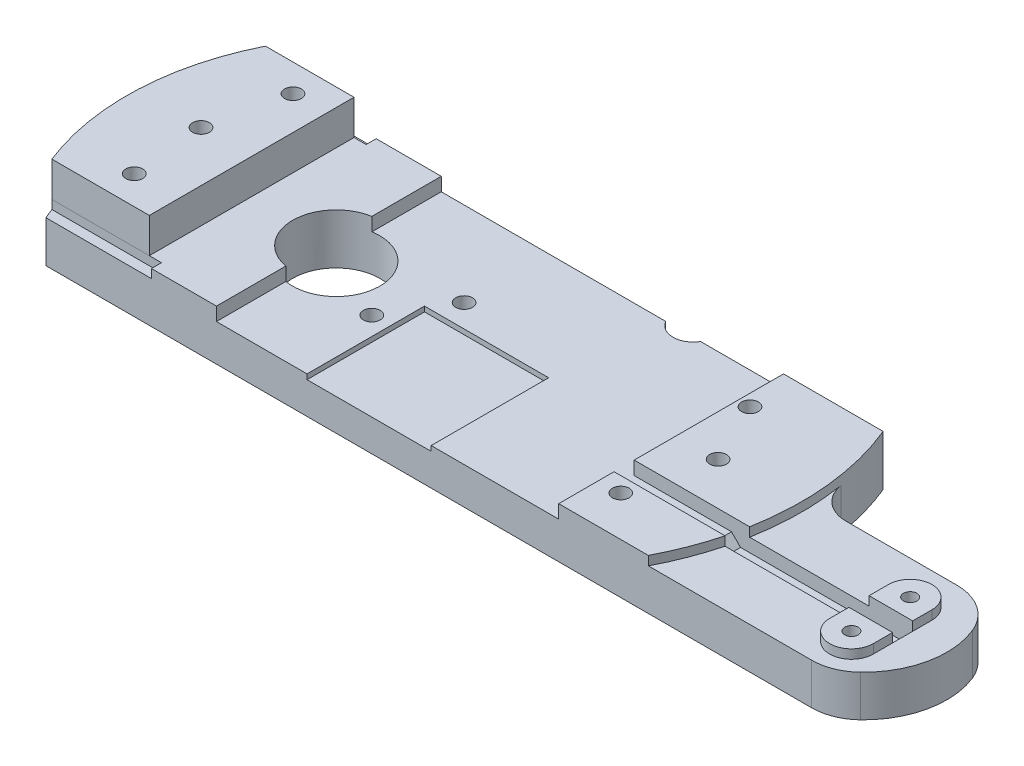
SolidWorks part; units mm, degrees
ref_plane "Front Plane" through (0, 0, 0) normal (0, 0, 1) x (1, 0, 0)
ref_plane "Top Plane" through (0, 0, 0) normal (0, 1, 0) x (1, 0, 0)
ref_plane "Right Plane" through (0, 0, 0) normal (1, 0, 0) x (0, 0, -1)
sketch "Sketch1" plane through (0, 0, 0) normal (0, 1, 0) x (1, 0, 0)
  line L1 (-97.5, -33.5) -> (97.5, -33.5)
  line L2 (-97.5, -33.5) -> (-97.5, 33.5)
  line L3 (-97.5, 33.5) -> (97.5, 33.5)
  line L4 (97.5, -33.5) -> (97.5, 33.5)
  line L5 (-97.5, -33.5) -> (97.5, 33.5) construction
  line L6 (-97.5, 33.5) -> (97.5, -33.5) construction
  point P0 (0, 0)
  dimension "D1" = 67
  dimension "D2" = 195
extrude "Boss-Extrude1" add sketch "Sketch1" along normal blind 25.4
sketch "Sketch2" plane through (0, 0, 0) normal (0, -1, 0) x (1, 0, 0)
  line L0 (-97.5, -33.5) -> (-97.5, 33.5) construction
  line L1 (97.5, 33.5) -> (97.5, -33.5) construction
  line L2 (97.5, 33.5) -> (88.5, 33.5)
  line L3 (-97.5, 33.5) -> (97.5, 33.5) construction
  line L4 (97.5, -33.5) -> (91.5, -33.5)
  line L5 (97.5, -33.5) -> (-97.5, -33.5) construction
  line L6 (-97.5, 33.5) -> (-91, 33.5)
  line L7 (-97.5, -33.5) -> (-88, -33.5)
  circle A0 centre (18.0922, -3.2198) radius 79.4078
  circle A1 centre (-22.6589, 2.9929) radius 74.8411
  line M7 (97.5, -33.5) -> (97.5, 33.5)
  line M8 (97.5, 33.5) -> (-97.5, 33.5)
  line M9 (-97.5, 33.5) -> (-97.5, -33.5)
  line M10 (-97.5, -33.5) -> (97.5, -33.5)
  dimension "D1" = 9
  dimension "D2" = 6
  dimension "D3" = 6.5
  dimension "D4" = 9.5
extrude "Cut-Extrude1" cut sketch "Sketch2" against normal through all contours A0 M7 M8 | A0 M10 M7 | A1 M9 M10 | A1 M8 M9 region at (94.8284, 0, 24.4273) region at (95.7123, 0, -25.9883) region at (-95.5654, 0, 25.941) region at (-94.6839, 0, -24.4966)
sketch "Sketch3" plane through (0, 0, 33.5) normal (0, 0, -1) x (-1, 0, 0)
  line L0 (97.5, 25.4) -> (63.2, 25.4)
  line L2 (63.2, 25.4) -> (63.2, 15)
  line L3 (63.2, 15) -> (40.2, 15)
  line L4 (40.2, 15) -> (40.2, 11)
  line L5 (40.2, 11) -> (-61.8, 11)
  line L6 (-91.5, 25.4) -> (88, 25.4) construction
  line L10 (97.5, 0) -> (97.5, 25.4) construction
  line L11 (-61.8, 11) -> (-61.8, 15)
  line L12 (-61.8, 15) -> (-97.5, 15)
  line L13 (-97.5, 25.4) -> (-97.5, 0) construction
  line L14 (-97.5, 15) -> (-97.5, 25.4)
  line L15 (-97.5, 25.4) -> (63.2, 25.4)
  line M13 (-88.5, 0) -> (-88.5, 25.4)
  line M14 (-88.5, 25.4) -> (91, 25.4)
  dimension "D1" = 10.4
  dimension "D2" = 34.3
  dimension "D3" = 23
  dimension "D4" = 4
  dimension "D5" = 102
extrude "Cut-Extrude2" cut sketch "Sketch3" along normal through all contours L11 L12 L2 L3 L4 L5 M13 M14 | L2 L3 L4 L5 L11 L12 L14 L15 region at (12.2699, 18.7206, 33.5)
sketch "Sketch4" plane through (0, 25.4, 0) normal (0, 1, 0) x (1, 0, 0)
  line L0 (-59.5873, 33.5) -> (-59.5873, 30.5)
  line L1 (-63.2, 33.5) -> (-88, 33.5) construction
  line L2 (-59.5873, 30.5) -> (-89.5873, 30.5)
  line L3 (-59.5873, -33.5) -> (-59.5873, -30.5)
  line L4 (-91, -33.5) -> (-63.2, -33.5) construction
  line L5 (-59.5873, -30.5) -> (-92.2617, -30.5)
  line L6 (-59.5873, 33.5) -> (-63.2, 33.5)
  line L7 (-59.5873, -33.5) -> (-63.2, -33.5)
  arc A0 (-88, 33.5) -> (-91, -33.5) centre (-22.6589, -2.9929) ccw construction
  line M5 (-91, -33.5) -> (-63.2, -33.5)
  line M6 (-63.2, -33.5) -> (-63.2, 33.5)
  line M7 (-63.2, 33.5) -> (-88, 33.5)
  arc M8 (-88, 33.5) -> (-91, -33.5) centre (-22.6589, -2.9929) ccw
  dimension "D1" = 3
  dimension "D2" = 3
  dimension "D3" = 30
extrude "Cut-Extrude3" cut sketch "Sketch4" against normal blind 13 contours L2 M6 M7 M8 | L0 L6 L2 M6 | L5 M6 M8 M5 | L7 L3 L5 M6 region at (-61.3937, 25.4, -32) region at (-76.0082, 25.4, -31.9845) region at (-77.4242, 25.4, 31.9889) region at (-61.3937, 25.4, 32)
sketch "Sketch6" plane through (0, 0, 0) normal (0, -1, 0) x (1, 0, 0)
  line L0 (-63.2, -33.5) -> (-97.5, -33.5)
  line L1 (91.5, -33.5) -> (-88, -33.5) construction
  line L2 (-63.2, -33.5) -> (-63.2, 33.5)
  line L3 (-91, 33.5) -> (88.5, 33.5) construction
  line L4 (-63.2, -9) -> (-28.1, -9) construction
  line L5 (-63.2, 8.7) -> (-18.7, 8.7) construction
  line L6 (-63.2, -8.3) -> (-8.2, -8.3) construction
  line L8 (91.5, -33.5) -> (-88, -33.5) construction
  line L9 (-97.5, -33.5) -> (-97.5, 33.5)
  line L10 (-97.5, 33.5) -> (-63.2, 33.5)
  circle A1 centre (-18.7, 8.7) radius 2.5
  circle A2 centre (74.1, -1.7) radius 2.5
  circle A3 centre (68.3, 21.5) radius 2.5
  circle A4 centre (65.3, -20) radius 2.5
  circle A5 centre (-8.2, -8.3) radius 2.5
  circle A6 centre (-76.2, 22) radius 2.5
  circle A7 centre (-78.2, 0.1) radius 2.5
  circle A8 centre (-73.2, -22.3) radius 2.5
  arc A10 (-91, 33.5) -> (-88, -33.5) centre (-22.6589, 2.9929) ccw construction
  dimension "D22" = 5
  dimension "D3" = 35.1
  dimension "D4" = 34.3
  dimension "D5" = 44.5
  dimension "D6" = 24.5
  dimension "D7" = 55
  dimension "D8" = 42.2
  dimension "D9" = 137.3
  dimension "D10" = 128.5
  dimension "D11" = 131.5
  dimension "D12" = 10
  dimension "D13" = 15
  dimension "D14" = 13
  dimension "D15" = 11.2
  dimension "D16" = 33.6
  dimension "D17" = 55.5
  dimension "D18" = 31.8
  dimension "D19" = 55
  dimension "D20" = 13.5
  dimension "D21" = 25.2
extrude "Cut-Extrude4" cut sketch "Sketch6" against normal through all contours A5 | A1 | A6 | A7 | A8 | A4 | A2 | A3 region at (-18.7, 0, 8.7) region at (74.1, 0, -1.7) region at (68.3, 0, 21.5) region at (65.3, 0, -20) region at (-8.2, 0, -8.3) region at (-76.2, 0, 22) region at (-78.2, 0, 0.1) region at (-73.2, 0, -22.3)
sketch "Sketch7" plane through (0, 11, 0) normal (0, 1, 0) x (1, 0, 0)
  line L1 (-13.2, 1.5) -> (23.8, 1.5)
  line L2 (-13.2, 1.5) -> (-13.2, -33.5)
  line L3 (-13.2, -33.5) -> (23.8, -33.5)
  line L4 (23.8, 1.5) -> (23.8, -33.5)
  line L8 (-63.2, 30.5) -> (-63.2, -30.5) construction
  line L9 (-63.2, 30.5) -> (-63.2, -30.5) construction
  line L10 (-40.2, -33.5) -> (61.8, -33.5) construction
  dimension "D1" = 50
  dimension "D2" = 87
  dimension "D3" = 35
extrude "Cut-Extrude5" cut sketch "Sketch7" against normal blind 1.5
sketch "Sketch8" plane through (0, 25.4, 0) normal (0, 1, 0) x (1, 0, 0)
  line L0 (-59.5873, -33.5) -> (-97.5, -33.5)
  line L1 (-97.5, -33.5) -> (-97.5, 33.5)
  line L3 (-97.5, 33.5) -> (31.9, 33.5)
  line L6 (31.9, 36.5) -> (31.9, 30.5)
  line L7 (31.9, 33.5) -> (37.0962, 33.5)
  line L10 (-59.5873, 33.5) -> (-88, 33.5) construction
  line L11 (-40.2, 33.5) -> (61.8, 33.5) construction
  circle A1 centre (31.9, 36.5) radius 6
  arc A2 (-89.5873, 30.5) -> (-92.2617, -30.5) centre (-22.6589, -2.9929) ccw construction
  dimension "D1" = 12
  dimension "D2" = 129.4
extrude "Cut-Extrude6" cut sketch "Sketch8" against normal blind 18.5 contours L6 A1 L7 | L3 A1 L6 region at (29.8648, 25.4, -32.2699) region at (33.9352, 25.4, -32.2699)
sketch "Sketch9" plane through (0, 0, 0) normal (0, -1, 0) x (1, 0, 0)
  line L0 (88.5, 33.5) -> (137.2004, 33.5)
  line L1 (139.5727, -7.5) -> (97.3846, -7.5)
  arc A0 (153.4738, 1.8643) -> (147.5429, 29.3643) centre (130.3054, 11.2571) ccw
  arc A1 (91.5, -33.5) -> (88.5, 33.5) centre (18.0922, -3.2198) ccw construction
  arc A2 (142.4281, -10.607) -> (147.5429, 29.3643) centre (130.3054, 11.2571) ccw construction
  arc A3 (147.5429, 29.3643) -> (137.2004, 33.5) centre (137.2004, 18.5) ccw
  arc A4 (147.5429, 29.3643) -> (137.9492, 33.4813) centre (137.2004, 18.5) ccw construction
  arc A5 (139.5727, -7.5) -> (153.4738, 1.8643) centre (139.5727, 7.5) ccw
  circle A6 centre (112.8948, -27.5) radius 16 construction
  circle A7 centre (103.3767, 59.4808) radius 16 construction
  circle A8 centre (112.8948, -27.5) radius 20 construction
  arc A9 (97.3846, -7.5) -> (88.5, 33.5) centre (18.0922, -3.2198) ccw
  circle A10 centre (138.3, 5.25) radius 2
  circle A11 centre (138.3, 22.75) radius 2
  circle A12 centre (138.3, 22.75) radius 2 construction
  circle A13 centre (138.3, 5.25) radius 2 construction
  dimension "D1" = 4
extrude "Boss-Extrude2" add sketch "Sketch9" against normal offset from surface (12.3 mm away) 1.3 up to face at (-16.2, 11, 8.7) offset beyond the face yes
fillet "Fillet1" radius 10 1 edges at (97.3846, 6.15, -7.5)
sketch "Sketch10" plane through (0, -3, 0) normal (0, -1, 0) x (1, 0, 0)
  circle A0 centre (-37.992, 0) radius 13
  dimension "D1" = 26
extrude "Cut-Extrude7" cut sketch "Sketch10" against normal up to surface (18 mm away) up to face at (-55.6437, 15, 0)
sketch "Sketch11" plane through (0, 12.3, 0) normal (0, 1, 0) x (1, 0, 0)
  line L0 (138.3, -5.25) -> (138.3, -22.75) construction
  line L1 (144.8, -5.25) -> (144.8, -22.75)
  line L2 (131.8, -5.25) -> (131.8, -22.75)
  line L3 (131.8, -11) -> (144.8, -11)
  line L4 (131.8, -17) -> (144.8, -17)
  line L5 (131.8, -14) -> (144.8, -14) construction
  arc A0 (144.8, -5.25) -> (131.8, -5.25) centre (138.3, -5.25) ccw
  arc A1 (131.8, -22.75) -> (144.8, -22.75) centre (138.3, -22.75) ccw
  point P4 (138.3, -14)
  circle M15 centre (138.3, -22.75) radius 2
  circle M16 centre (138.3, -5.25) radius 2
  dimension "D1" = 13
  dimension "D2" = 6
extrude "Boss-Extrude3" add sketch "Sketch11" along normal up to surface (2.7 mm away) contours L1 A0 L2 L3 M16 | L2 A1 L1 L4 M15 region at (144.6214, 12.3, 8.125) region at (144.6214, 12.3, 19.875) up to face at (70.8, 15, 21.5)
split "Split1" bodies to split 113 resulting bodies 114 115 split by face at (-53.6341, 15, 0)
sketch "Sketch12" plane through (0, 0, 11) normal (0, 0, 1) x (1, 0, 0)
  line L0 (144.8, 15) -> (144.8, 8.3)
  line L1 (144.8, 8.3) -> (93.5, 8.3)
  line L3 (97.5, 12.3) -> (88.5, 12.3) construction
  line L4 (90.8, 11) -> (61.8, 11)
  line L5 (61.8, 11) -> (61.8, 15)
  line L6 (61.8, 15) -> (88.5, 15) construction
  line L7 (61.8, 15) -> (144.8, 15)
  line L10 (97.5, 12.3) -> (93.5, 12.3) construction
  line L12 (88.5, 12.3) -> (137.2004, 12.3) construction
  line L13 (93.5, 12.3) -> (93.5, 8.3) construction
  line L14 (61.8, 11) -> (61.8, 15) construction
  line L15 (23.8, 11) -> (61.8, 11) construction
  line L16 (93.5, 8.3) -> (90.8, 11)
  dimension "D1" = 45
extrude "Cut-Extrude8" cut sketch "Sketch12" along normal up to surface (6 mm away) up to face at (138.3, 13.65, 17)
